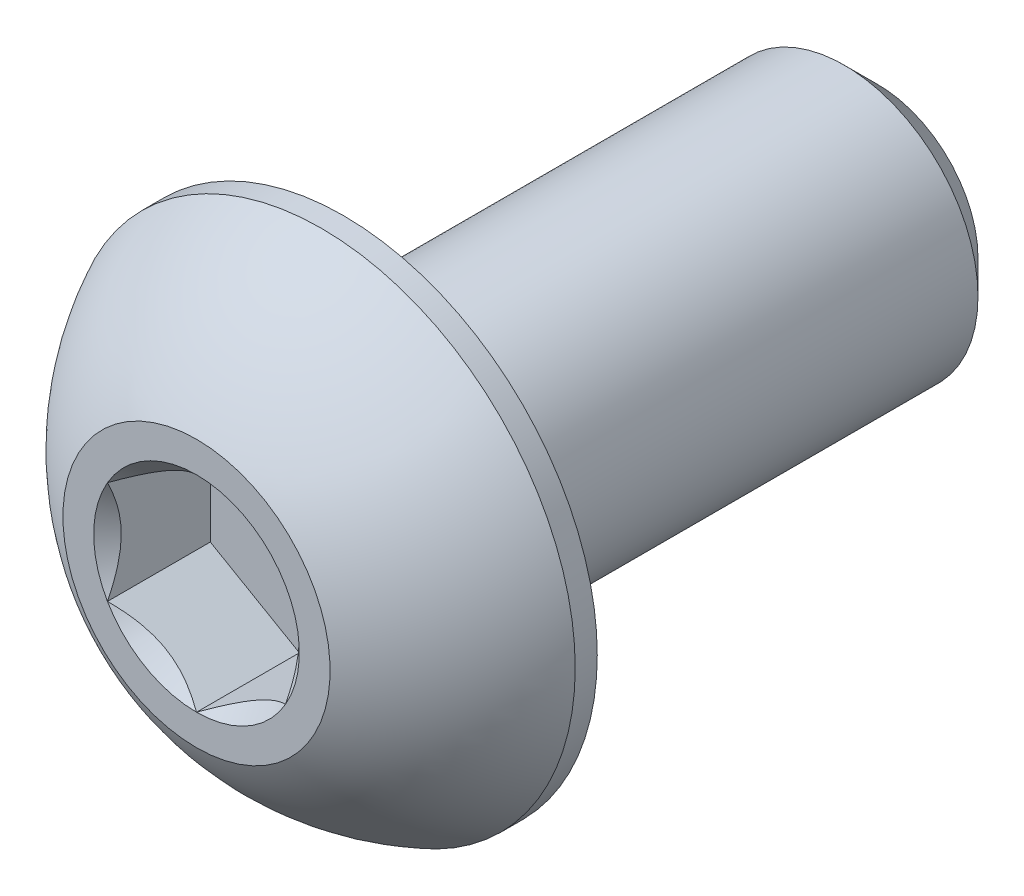
SolidWorks part; units mm, degrees
ref_plane "Front" through (0, 0, 0) normal (0, 0, 1) x (1, 0, 0)
ref_plane "Top" through (0, 0, 0) normal (0, 1, 0) x (1, 0, 0)
ref_plane "Right" through (0, 0, 0) normal (1, 0, 0) x (0, 0, -1)
sketch "Sketch1" plane through (0, 0, 0) normal (1, 0, 0) x (0, 0, -1)
  line L2 (1.65, 1.5) -> (7.65, 1.5)
  line L3 (7.65, 1.5) -> (7.65, 0)
  line L4 (7.65, 0) -> (1.65, 0)
  line L6 (1.4025, 2.85) -> (1.65, 2.85) construction
  line L7 (7.65, 1.5) -> (7.65, -1.5) construction
  line L8 (0, 0) -> (1.65, 0) construction
  line L9 (1.65, 2.85) -> (1.65, -2.85) construction
  line L11 (1.65, 1.5) -> (1.65, 0)
  line L13 (0, 1) -> (0, -1) construction
  line L14 (0, 1) -> (0, 1.5) construction
  line L15 (7.6187, 1.5541) -> (7.8687, 1.1211) construction
  line L16 (7.8687, 1.1211) -> (8.1187, 1.5541) construction
  line L17 (8.1187, 1.5541) -> (7.6187, 1.5541) construction
  line L18 (7.65, 1.5) -> (8.0875, 1.5) construction
  line L19 (7.8687, 1.5541) -> (7.8687, 1.5) construction
  line L20 (7.8687, 1.5) -> (7.8687, 1.1752) construction
  line L21 (7.8687, 1.1752) -> (7.8687, 1.1211) construction
  line L22 (7.8375, 1.1752) -> (7.9, 1.1752)
  line L23 (7.6344, 1.5271) -> (8.1031, 1.5271)
  line L24 (7.9, 1.1752) -> (8.1031, 1.5271)
  line L25 (7.8375, 1.1752) -> (7.6344, 1.5271)
  line L26 (7.275, 1.5) -> (7.65, 1.125)
  arc A3 (0, 1.5) -> (1.4025, 2.85) centre (2.7948, 0) cw construction
  point P29 (7.8687, 1.5271)
  point P30 (6.4, -1.5)
  dimension "D1" = 0.2475
  dimension "Pitch" = 0.5
  dimension "D3" = 0.0625
  dimension "D2" = 0.375
  dimension "D4" = 45
  dimension "D5" = 1.25
sketch "Sketch10" plane through (0, 0, 0) normal (1, 0, 0) x (0, 0, -1)
  line L0 (7.275, 1.5) -> (7.65, 1.125) construction
  line L1 (7.275, 1.5) -> (7.65, 1.125)
  line L4 (7.65, 1.5) -> (1.65, 1.5)
  line L5 (7.65, 0) -> (7.65, 1.5)
  line L6 (1.65, 0) -> (7.65, 0)
  line L7 (1.65, 1.5) -> (1.65, 0)
  line L8 (7.275, 1.5) -> (1.65, 1.5)
  line L9 (7.65, 0) -> (7.65, 1.125)
  line L10 (1.65, 0) -> (7.65, 0)
  line L11 (1.65, 1.5) -> (1.65, 0)
  dimension "D1" = 0
revolve "Revolve3" add sketch "Sketch10" angle 360 about L8
sketch "Sketch7" plane through (0, 0, 0) normal (1, 0, 0) x (0, 0, -1)
  line L6 (1.4025, 2.85) -> (1.65, 2.85) construction
  line L8 (0, 0) -> (1.65, 0) construction
  line L11 (1.65, 2.85) -> (1.65, -2.85) construction
  line L12 (1.4025, 2.85) -> (1.65, 2.85)
  line L13 (0, 0) -> (1.65, 0)
  line L14 (0, 1) -> (0, -1) construction
  line L15 (1.65, 2.85) -> (1.65, 0)
  line L16 (0, 1.5) -> (0, 0)
  arc A2 (1.4025, 2.85) -> (0, 1.5) centre (2.7948, 0) ccw construction
  arc A3 (1.4025, 2.85) -> (0, 1.5) centre (2.7948, 0) ccw
revolve "Revolve2" add sketch "Sketch7" angle 360 mid plane about L13
sketch "Sketch5" plane through (0, 0, 0) normal (0, 0, 1) x (1, 0, 0)
  line L1 (1, -0.5774) -> (1, 0.5774)
  line L2 (1, 0.5774) -> (0, 1.1547)
  line L3 (0, 1.1547) -> (-1, 0.5774)
  line L4 (-1, 0.5774) -> (-1, -0.5774)
  line L5 (-1, -0.5774) -> (0, -1.1547)
  line L6 (0, -1.1547) -> (1, -0.5774)
  circle A0 centre (0, 0) radius 1 construction
extrude "Cut-Extrude2" cut sketch "Sketch5" against normal blind 1.155
sketch "Sketch6" plane through (0, 0, 0) normal (0, 0, 1) x (1, 0, 0)
  circle A0 centre (0, 0) radius 1.1547
extrude "Cut-Extrude3" cut sketch "Sketch6" against normal blind 1.155 draft 45
sketch "Sketch9" [suppressed] plane through (0, 0, -1.65) normal (0, 0, -1) x (-1, 0, 0)
  circle A0 centre (0, 0) radius 1.5 construction
  circle A4 centre (0, 0) radius 1.5
split "Split1" [suppressed] bodies to split 113
sketch "Sketch11" [suppressed] plane through (0, 0, -7.65) normal (0, 0, -1) x (-1, 0, 0)
  circle A0 centre (0, 0) radius 1.5 construction
  circle A1 centre (0, 0) radius 1.5
curve "Helix/Spiral1" [suppressed] pitch 0.5 height 7.65 turns 15.3
sketch "Sketch12" [suppressed] plane through (0, 0, 0) normal (1, 0, 0) x (0, 0, -1)
  line L0 (7.8375, 1.1752) -> (7.9, 1.1752) construction
  line L1 (7.9, 1.1752) -> (8.1031, 1.5271) construction
  line L2 (7.6344, 1.5271) -> (8.1031, 1.5271) construction
  line L3 (7.8375, 1.1752) -> (7.6344, 1.5271) construction
  line L4 (7.8375, 1.1752) -> (7.9, 1.1752)
  line L5 (7.9, 1.1752) -> (8.1031, 1.5271)
  line L6 (7.6344, 1.5271) -> (8.1031, 1.5271)
  line L7 (7.8375, 1.1752) -> (7.6344, 1.5271)
sweep "Cut-Sweep2" [suppressed] cut profiles "Sketch12" path "Helix/Spiral1"
extrude "Boss-Extrude1" [suppressed] add sketch "Sketch9" along normal blind 10 draft 45
equation "\"D1@Cut-Extrude2\" = \"Head Ht@Sketch1\" * .7"
equation "\"D1@Sketch1\" = \"Head Ht@Sketch1\" * .15"
equation "\"D1@Cut-Extrude3\" = \"D1@Cut-Extrude2\""
equation "\"D3@Sketch1\" = \"Pitch@Sketch1\" / 8"
equation "\"D2@Sketch1\"=\"Pitch@Sketch1\"*0.75"
equation "\"D3@Helix/Spiral1\" = \"Lg@Sketch1\" + \"Head Ht@Sketch1\""
equation "\"D4@Helix/Spiral1\"=\"pitch@sketch1\""
equation "\"D5@Sketch1\"=\"Pitch@Sketch1\"*2.5"
